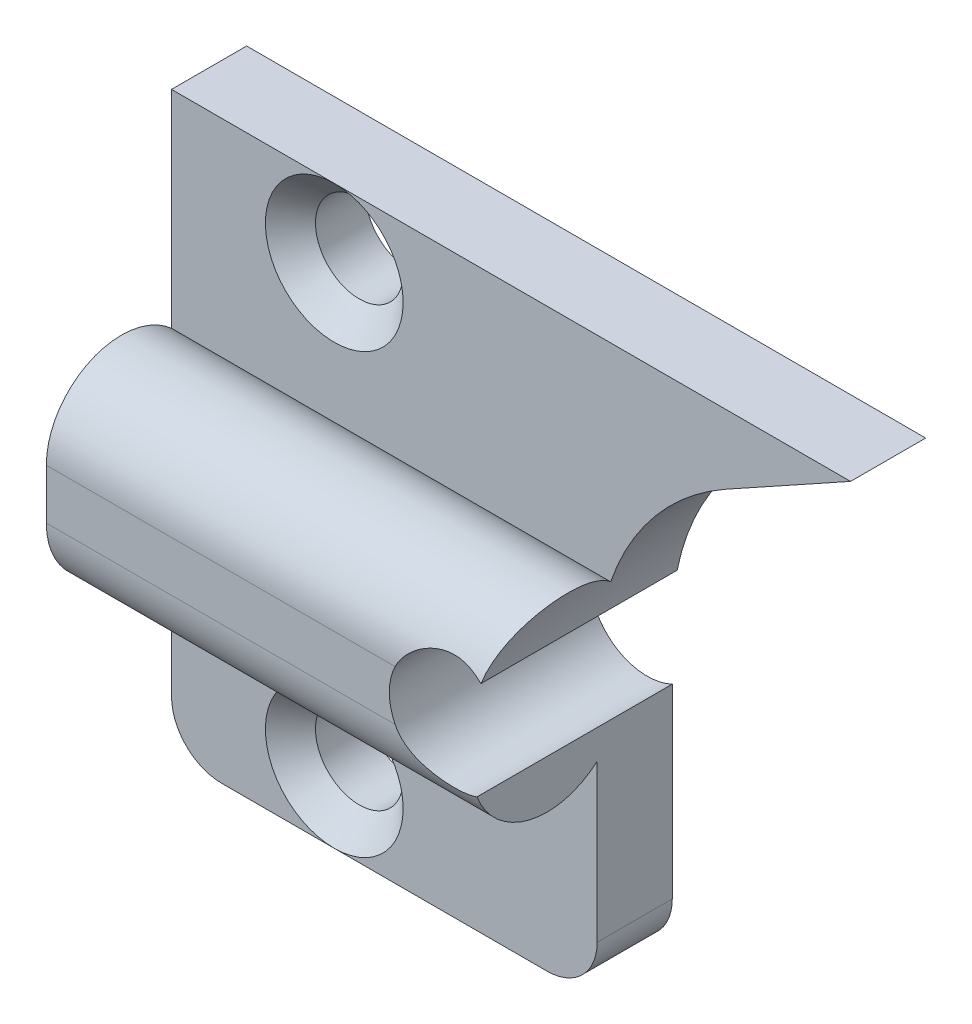
SolidWorks part; units mm, degrees
ref_plane "Alzado" through (0, 0, 0) normal (0, 0, 1) x (1, 0, 0)
ref_plane "Planta" through (0, 0, 0) normal (0, 1, 0) x (1, 0, 0)
ref_plane "Vista lateral" through (0, 0, 0) normal (1, 0, 0) x (0, 0, -1)
sketch "Guia" plane through (0, 0, 0) normal (0, 0, 1) x (1, 0, 0)
  line L0 (0, 0) -> (49, 0)
  line L1 (49, 0) -> (32.8558, 29.1248)
  dimension "D1" = 49
  dimension "D2" = 33.3
  dimension "D3" = 61
ref_plane "Plano1" through (0, 0, -3) normal (0, 0, 1) x (1, 0, 0)
sketch "Croquis3" plane through (0, 0, -3) normal (0, 0, 1) x (1, 0, 0)
  line L0 (9.5, 8.75) -> (9.5, -8.75) construction
  line L1 (3, 11.5) -> (41, 11.5)
  line L2 (3, 11.5) -> (3, -11.5)
  line L3 (3, -11.5) -> (41, -11.5)
  line L4 (41, 11.5) -> (41, -11.5)
  circle A0 centre (9.5, 8.75) radius 1.75
  circle A1 centre (9.5, -8.75) radius 1.75
  arc A2 (20.1847, -1.9129) -> (20.1847, 1.9129) centre (30, 0) ccw
  arc A3 (20.1847, 1.9129) -> (20.1847, -1.9129) centre (19, 0) ccw
  point P4 (3, 0)
  point P8 (9.5, 0)
  dimension "D5" = 3.5
  dimension "D6" = 3.5
  dimension "D7" = 11
  dimension "D8" = 20
  dimension "D10" = 4.5
  dimension "D1" = 38
  dimension "D2" = 23
  dimension "D3" = 31.5
  dimension "D4" = 17.5
  dimension "D9" = 22
  dimension "D11" = 3
extrude "Saliente-Extruir1" add sketch "Croquis3" along normal blind 1
sketch "Croquis4" plane through (3, 0, 0) normal (1, 0, 0) x (0, 0, -1)
  line L0 (0, 1) -> (0, -1) construction
  line L1 (3, 1) -> (3, -1)
  line L2 (-3, 1) -> (-3, -1)
  arc A0 (3, 1) -> (-3, 1) centre (0, 1) ccw
  arc A1 (-3, -1) -> (3, -1) centre (0, -1) ccw
  point P3 (0, 0)
  dimension "D1" = 6
  dimension "D2" = 2
extrude "Saliente-Extruir2" add sketch "Croquis4" along normal blind 25
ref_plane "Plano3" through (49, 0, 0) normal (-0.4848, 0.8746, 0) x (0.8746, 0.4848, 0)
sketch "Croquis8" plane through (49, 0, 0) normal (-0.4848, 0.8746, 0) x (0.8746, 0.4848, 0)
  line L0 (-1, 0) -> (1, 0) construction
  line L1 (-1, 3) -> (1, 3)
  line L2 (-1, -3) -> (1, -3)
  arc A0 (-1, 3) -> (-1, -3) centre (-1, 0) ccw
  arc A1 (1, -3) -> (1, 3) centre (1, 0) ccw
  point P2 (0, 0)
  dimension "D1" = 6
  dimension "D2" = 2
extrude "Saliente-Extruir4" add sketch "Croquis8" along normal blind 40 separate body
sketch "Croquis9" plane through (0, 0, -3) normal (0, 0, 1) x (1, 0, 0)
  line L4 (25.1519, 8.7462) -> (39.6861, 16.8027)
  line L6 (49, 0) -> (32.8558, 29.1248) construction
  line L7 (39.6861, 16.8027) -> (36.2925, 22.925)
  line L8 (36.2925, 22.925) -> (21.7582, 14.8685)
  line L9 (13, 0) -> (20, 0)
  arc A1 (25.1519, 8.7462) -> (20, 0) centre (30, 0) ccw
  arc A2 (21.7582, 14.8685) -> (13, 0) centre (30, 0) ccw
  dimension "D1" = 10
  dimension "D2" = 7
extrude "Saliente-Extruir5" add sketch "Croquis9" along normal blind 6
sketch "Croquis10" plane through (0, 0, -3) normal (0, 0, -1) x (-1, 0, 0)
  line L0 (-54.7522, 25.1539) -> (-25.1519, 8.7462)
  line L1 (-20, -2.0712) -> (-20, -15.3934)
  line L2 (-20, -15.3934) -> (-54.7522, -15.3934)
  line L3 (-54.7522, -15.3934) -> (-54.7522, 25.1539)
  line L4 (-30.1199, 11.5) -> (-38.8115, 16.3178) construction
  arc A0 (-20, -2.0712) -> (-20.195, 1.9652) centre (-19, 0) ccw
  arc A1 (-20.195, 1.9652) -> (-25.1519, 8.7462) centre (-30, 0) ccw
  dimension "D1" = 4.6
  dimension "D2" = 10
extrude "Cortar-Extruir3" cut sketch "Croquis10" against normal through all
sketch "Croquis5" plane through (3, 0, 0) normal (1, 0, 0) x (0, 0, -1)
  circle A0 centre (0, 0) radius 1.75
  dimension "D1" = 3.5
extrude "Cortar-Extruir1" cut sketch "Croquis5" along normal blind 12
sketch "Croquis11" plane through (-7.8754, 14.2076, 0) normal (-0.4848, 0.8746, 0) x (0.8746, 0.4848, 0)
  line L0 (42.8564, 3) -> (42.8564, -3) construction
  line L1 (43.8564, 3) -> (41.8564, 3) construction
  line L2 (41.8564, -3) -> (43.8564, -3) construction
  circle A0 centre (42.8564, 0) radius 1.75
  dimension "D1" = 3.5
extrude "Cortar-Extruir4" cut sketch "Croquis11" against normal through all
sketch "Croquis12" plane through (0, 0, -3) normal (0, 0, -1) x (-1, 0, 0)
  line L0 (-41.8182, 31.0299) -> (-23.8934, 27.2198)
  line L1 (-49, 0) -> (-32.8558, 29.1248) construction
  line L2 (-41.8182, 31.0299) -> (-26.8491, 44.5194)
  line L3 (-26.8491, 44.5194) -> (-23.8934, 27.2198)
  point P2 (-32.8558, 29.1248)
  dimension "D1" = 73
extrude "Cortar-Extruir5" cut sketch "Croquis12" against normal through all
fillet "Redondeo1" radius 2 3 edges at (3, 11.5, -2.5) (3, -11.5, -2.5) (20, -11.5, -2.5)
sketch "Croquis13" plane through (0, 0, -3) normal (0, 0, -1) x (-1, 0, 0)
  line L9 (-20, -2.0712) -> (-20, -9.5)
  line L10 (-18, -11.5) -> (-5, -11.5)
  line L11 (-3, -9.5) -> (-3, 9.5)
  line L12 (-5, 11.5) -> (-17.48, 11.5)
  line L13 (-21.7582, 14.8685) -> (-35.4178, 22.4402)
  line L14 (-35.4178, 22.4402) -> (-31.833, 28.9074)
  line L15 (-31.833, 28.9074) -> (-33.8787, 29.3422)
  line L16 (-33.8787, 29.3422) -> (-40.5608, 17.2875)
  line L17 (-40.5608, 17.2875) -> (-25.1519, 8.7462)
  line L18 (-20, -2.0712) -> (-20, -9.5)
  line L19 (-18, -11.5) -> (-5, -11.5)
  line L20 (-3, -9.5) -> (-3, 9.5)
  line L21 (-5, 11.5) -> (-17.48, 11.5)
  line L22 (-21.7582, 14.8685) -> (-35.4178, 22.4402)
  line L23 (-35.4178, 22.4402) -> (-31.833, 28.9074)
  line L24 (-31.833, 28.9074) -> (-33.8787, 29.3422)
  line L25 (-33.8787, 29.3422) -> (-40.5608, 17.2875)
  line L26 (-40.5608, 17.2875) -> (-25.1519, 8.7462)
  circle A3 centre (-9.5, -8.75) radius 1.75 construction
  circle A4 centre (-9.5, 8.75) radius 1.75 construction
  circle A5 centre (-9.5, -8.75) radius 1.75
  circle A6 centre (-9.5, 8.75) radius 1.75
  arc A9 (-20, -9.5) -> (-18, -11.5) centre (-18, -9.5) ccw
  arc A10 (-5, -11.5) -> (-3, -9.5) centre (-5, -9.5) ccw
  arc A11 (-3, 9.5) -> (-5, 11.5) centre (-5, 9.5) ccw
  arc A12 (-17.48, 11.5) -> (-21.7582, 14.8685) centre (-30, 0) ccw
  arc A13 (-20.195, 1.9652) -> (-25.1519, 8.7462) centre (-30, 0) ccw
  arc A14 (-20, -2.0712) -> (-20.195, 1.9652) centre (-19, 0) ccw
  arc A15 (-20, -9.5) -> (-18, -11.5) centre (-18, -9.5) ccw
  arc A16 (-5, -11.5) -> (-3, -9.5) centre (-5, -9.5) ccw
  arc A17 (-3, 9.5) -> (-5, 11.5) centre (-5, 9.5) ccw
  arc A18 (-17.48, 11.5) -> (-21.7582, 14.8685) centre (-30, 0) ccw
  arc A19 (-20.195, 1.9652) -> (-25.1519, 8.7462) centre (-30, 0) ccw
  arc A20 (-20, -2.0712) -> (-20.195, 1.9652) centre (-19, 0) ccw
  dimension "D1" = 0
extrude "Saliente-Extruir6" add sketch "Croquis13" along normal blind 2
chamfer "Chaflán1" distance 1 angle 45 2 edges at (11.25, -8.75, -2) (11.25, 8.75, -2)
extrude "Cortar-Extruir6" cut sketch "Croquis14" against normal through all
sketch "Croquis14" plane through (3, 0.0247, -35.3274) normal (-1, 0, 0) x (0, 0, 1)
  line L1 (-38.6726, 3.2113) -> (-38.6726, 11.4753)
  line L2 (-38.6726, 11.4753) -> (-35.6726, 11.4753)
  line L3 (33.3274, 11.4753) -> (33.3274, 3.2113)
  line L4 (-43.6726, 0.9753) -> (-43.6726, 29.9697)
  line L5 (-43.6726, 29.9697) -> (-35.6726, 29.9697)
  line L6 (38.3274, 29.9697) -> (38.3274, 0.9753)
  line L7 (-35.6726, 11.4753) -> (-35.6726, 29.9697)
  line L8 (30.3274, 11.4753) -> (30.3274, 29.9697)
  line L9 (30.3274, 11.4753) -> (33.3274, 11.4753)
  line L10 (30.3274, 29.9697) -> (38.3274, 29.9697)
  arc A0 (38.3274, 0.9753) -> (33.3274, 3.2113) centre (35.3274, 0.9753) ccw
  arc A2 (-38.6726, 3.2113) -> (-43.6726, 0.9753) centre (-40.6726, 0.9753) ccw
sketch "Croquis15" plane through (0, 0, -2) normal (0, 0, 1) x (1, 0, 0)
  line L0 (3, 9.5) -> (3, 11.5)
  line L1 (3, 11.5) -> (5, 11.5)
  arc A0 (5, 11.5) -> (3, 9.5) centre (5, 9.5) ccw
extrude "Saliente-Extruir7" add sketch "Croquis15" against normal up to surface (3 mm away) up to face at (14.4911, -0.0564, -5)
